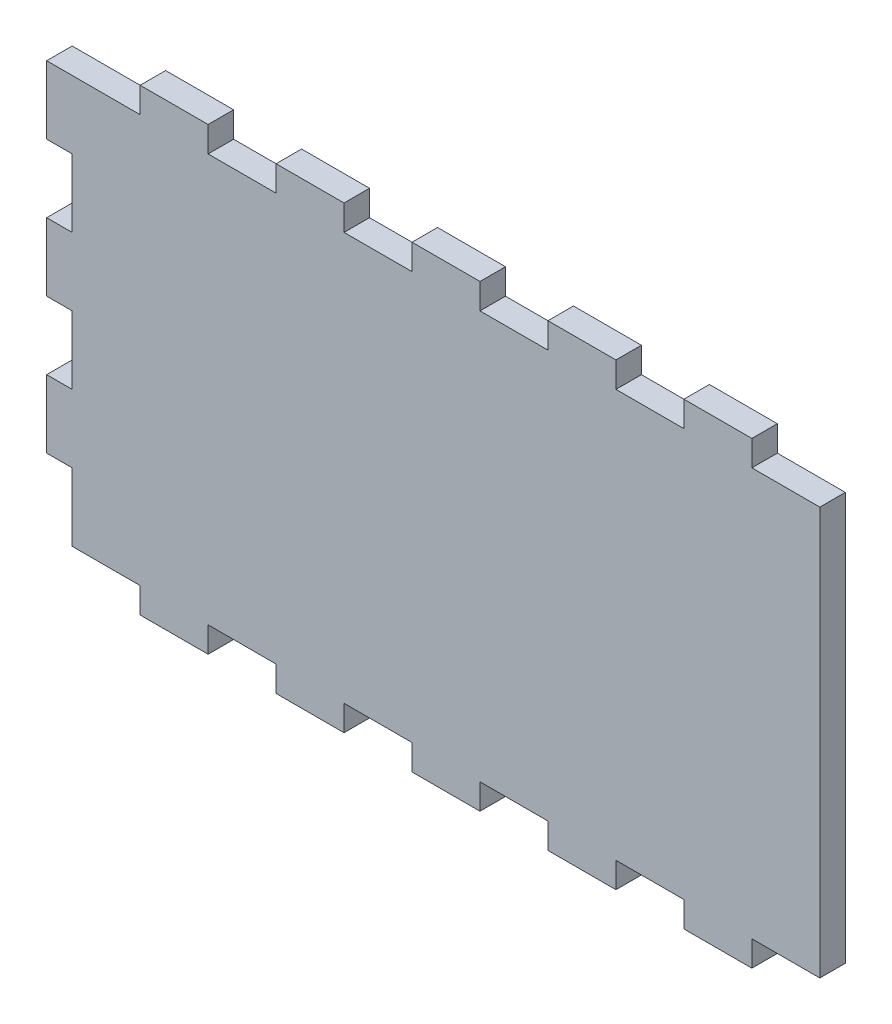
SolidWorks part; units mm, degrees
ref_plane "Front Plane" through (0, 0, 0) normal (0, 0, 1) x (1, 0, 0)
ref_plane "Top Plane" through (0, 0, 0) normal (0, 1, 0) x (1, 0, 0)
ref_plane "Right Plane" through (0, 0, 0) normal (1, 0, 0) x (0, 0, -1)
sketch "Sketch1" plane through (0, 0, 0) normal (0, 0, 1) x (1, 0, 0)
  line L1 (-139.7, -76.2) -> (139.7, -76.2)
  line L2 (-139.7, -76.2) -> (-139.7, 76.2)
  line L3 (-139.7, 76.2) -> (139.7, 76.2)
  line L4 (139.7, -76.2) -> (139.7, 76.2)
  line L5 (-139.7, -76.2) -> (139.7, 76.2) construction
  line L6 (-139.7, 76.2) -> (139.7, -76.2) construction
  point P0 (0, 0)
  dimension "D1" = 279.4
  dimension "D2" = 152.4
extrude "Boss-Extrude1" add sketch "Sketch1" along normal blind 9.525
sketch "Sketch2" plane through (0, -76.2, 0) normal (0, -1, 0) x (1, 0, 0)
  line L0 (-139.7, 0) -> (139.7, 0) construction
  line L1 (-114.3, 0) -> (-88.9, 0)
  line L2 (-114.3, 0) -> (-114.3, 9.525)
  line L3 (-114.3, 9.525) -> (-88.9, 9.525)
  line L4 (-88.9, 0) -> (-88.9, 9.525)
  line L5 (-139.7, 9.525) -> (139.7, 9.525) construction
  line L6 (-139.7, 9.525) -> (-139.7, 0) construction
  point P10 (-139.7, 4.7625)
  dimension "D1" = 25.4
  dimension "D2" = 25.4
extrude "Boss-Extrude2" add sketch "Sketch2" along normal blind 9.525
pattern_linear "LPattern1" count 5 spacing 50.8 along (1, 0, 0) of "Boss-Extrude2"
mirror "Mirror1" about plane through (0, 0, 0) normal (0, 1, 0) of "LPattern1"
sketch "Sketch3" plane through (-139.7, 0, 0) normal (-1, 0, 0) x (0, 0, 1)
  line L0 (0, 76.2) -> (0, -76.2) construction
  line L1 (9.525, 76.2) -> (0, 76.2)
  line L2 (9.525, 76.2) -> (9.525, 50.8)
  line L3 (9.525, 50.8) -> (0, 50.8)
  line L4 (0, 76.2) -> (0, 50.8)
  dimension "D1" = 25.4
extrude "Boss-Extrude3" add sketch "Sketch3" along normal blind 9.525
pattern_linear "LPattern2" count 3 spacing 50.8 along (0, -1, 0) of "Boss-Extrude3"
